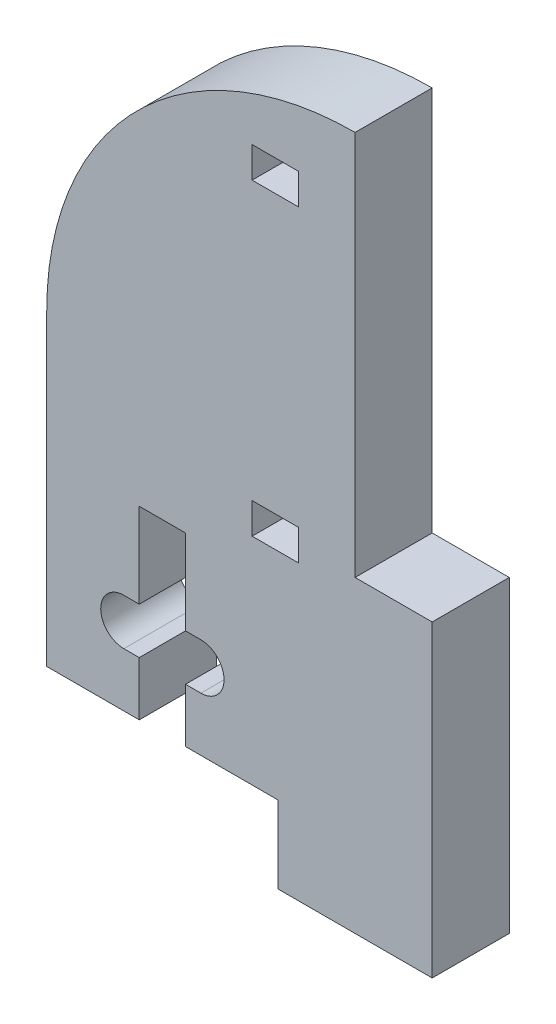
SolidWorks part; units mm, degrees
ref_plane "Front Plane" through (0, 0, 0) normal (0, 0, 1) x (1, 0, 0)
ref_plane "Top Plane" through (0, 0, 0) normal (0, 1, 0) x (1, 0, 0)
ref_plane "Right Plane" through (0, 0, 0) normal (1, 0, 0) x (0, 0, -1)
sketch "Sketch1" plane through (0, 0, 0) normal (0, 0, 1) x (1, 0, 0)
  line L0 (6.3217, -6.0204) -> (3.3217, -6.0204)
  line L1 (10, -20) -> (-10, -20)
  line L2 (10, -5) -> (10, 20)
  line L3 (10, -20) -> (15, -20)
  line L4 (-10, -20) -> (-10, 0)
  line L5 (10, -20) -> (-10, 20) construction
  line L6 (10, 20) -> (-10, -20) construction
  line L7 (6.3217, 15.9796) -> (3.3217, 15.9796)
  line L8 (10, -5) -> (15, -5)
  line L9 (15, -20) -> (15, -5)
  line L10 (6.3217, 15.9796) -> (6.3217, 13.9796)
  line L11 (6.3217, 13.9796) -> (3.3217, 13.9796)
  line L12 (3.3217, 15.9796) -> (3.3217, 13.9796)
  line L13 (3.3217, -4.0204) -> (3.3217, -6.0204)
  line L14 (6.3217, -4.0204) -> (6.3217, -6.0204)
  line L15 (6.3217, -4.0204) -> (3.3217, -4.0204)
  line L17 (15, -20) -> (5, -20)
  line L18 (15, -20) -> (15, -25)
  line L19 (15, -25) -> (5, -25)
  line L20 (5, -20) -> (5, -25)
  arc A0 (10, 20) -> (-10, 0) centre (10, 0) ccw
  point P0 (0, 0)
  dimension "D1" = 20
  dimension "D2" = 40
  dimension "D3" = 5
  dimension "D4" = 15
  dimension "D5" = 3
  dimension "D6" = 2
  dimension "D8" = 5
  dimension "D9" = 10
  dimension "D10" = 20
  dimension "D11" = 5
  dimension "D7" = 2
extrude "Boss-Extrude1" add sketch "Sketch1" along normal blind 5 contours L2 A0 L4 L1 L3 L9 L8 L12 L7 L10 L11 L15 L14 L0 L13 | L1 L20 L19 L18 L3 region at (10, -22.5, 0) region at (1.743, -2.9989, 0)
sketch "Sketch2" plane through (0, 0, 5) normal (0, 0, 1) x (1, 0, 0)
  line L0 (5, -20) -> (-10, -20) construction
  line L1 (-1, -20) -> (-4, -20)
  line L2 (-1, -20) -> (-1, -8)
  line L3 (-1, -8) -> (-4, -8)
  line L4 (-4, -20) -> (-4, -8)
  line L5 (-5, -15) -> (0, -15) construction
  line L6 (-5, -13.5) -> (0, -13.5)
  line L7 (-5, -16.5) -> (0, -16.5)
  line L8 (-2.5, -8) -> (-2.5, -15) construction
  line L9 (-2.5, -20) -> (-2.5, -15) construction
  arc A0 (-5, -13.5) -> (-5, -16.5) centre (-5, -15) ccw
  arc A1 (0, -16.5) -> (0, -13.5) centre (0, -15) ccw
  point P8 (-2.5, -15)
  dimension "D1" = 3
  dimension "D2" = 8
  dimension "D3" = 3
  dimension "D4" = 12
  dimension "D5" = 5
extrude "Cut-Extrude1" cut sketch "Sketch2" against normal blind 10 contours L6 A1 L7 A0 | L2 L3 L4 L1
